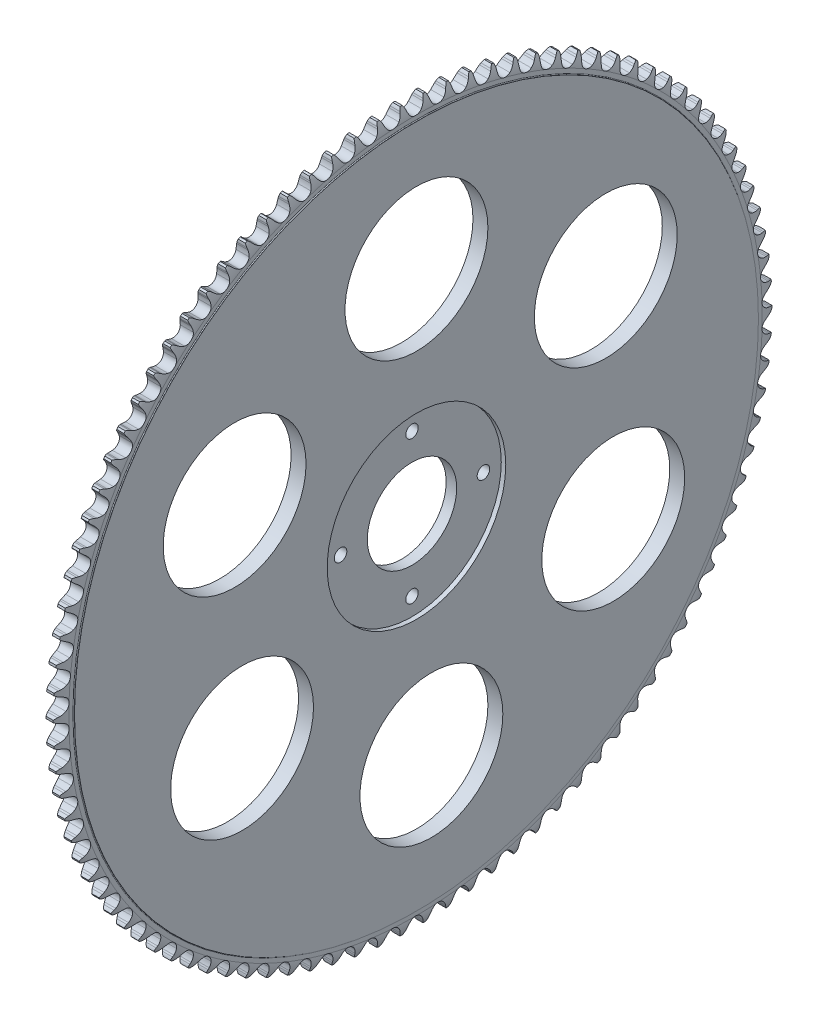
SolidWorks part; units mm, degrees
material "45"
ref_plane "前视基准面" through (0, 0, 0) normal (0, 0, 1) x (1, 0, 0)
ref_plane "上视基准面" through (0, 0, 0) normal (0, 1, 0) x (1, 0, 0)
ref_plane "右视基准面" through (0, 0, 0) normal (1, 0, 0) x (0, 0, -1)
sketch "草图1" plane through (0, 0, 0) normal (0, 0, 1) x (1, 0, 0)
  line L0 (-12.7, 0) -> (12.7, 0) construction
  line L1 (-8.3587, 50) -> (-8.3587, 383)
  line L2 (-8.3587, 383) -> (-8.1517, 383)
  line L3 (-7.3237, 383.8279) -> (-7.3237, 388.2963)
  line L4 (-4.0217, 402.5) -> (4.0217, 402.5)
  line L5 (7.3237, 388.2963) -> (7.3237, 383.8279)
  line L6 (8.1517, 383) -> (8.3587, 383)
  line L7 (8.3587, 383) -> (8.3587, 50)
  line L8 (8.3587, 50) -> (-8.3587, 50)
  line L9 (0, 0) -> (0, 402.5) construction
  line L10 (-6.5678, 396.2363) -> (6.5678, 396.2363) construction
  line L11 (-6.5678, -396.2363) -> (6.5678, -396.2363) construction
  line L12 (12.7, 0) -> (110.7, 0) construction
  line L13 (-7.3237, 388.2963) -> (3.7984, 388.2963) construction
  line L14 (-7.3237, -388.2963) -> (3.7984, -388.2963) construction
  line L15 (110.7, 0) -> (126.58, 0) construction
  line L16 (126.58, 0) -> (150.71, 0) construction
  line L17 (150.71, 0) -> (166.46, 0) construction
  line L18 (166.46, 0) -> (195.75, 0) construction
  arc A0 (-4.0217, 402.5) -> (-7.3237, 388.2963) centre (18.0263, 389.8887) ccw
  arc A1 (4.0217, 402.5) -> (7.3237, 388.2963) centre (-18.0263, 389.8887) cw
  arc A2 (7.3237, 383.8279) -> (8.1517, 383) centre (8.1517, 383.8279) ccw
  arc A3 (-8.1517, 383) -> (-7.3237, 383.8279) centre (-8.1517, 383.8279) ccw
  point P30 (7.3237, 383)
  point P33 (-7.3237, 383)
  dimension "D1" = 5.2963
  dimension "rx" = 25.4
  dimension "D3" = 0.8279
  dimension "d" = 792.4727
  dimension "p" = 25.4
  dimension "z" = 98
  dimension "da" = 805
  dimension "df" = 776.5927
  dimension "dr" = 15.88
  dimension "dk" = 100
  dimension "dg" = 766
  dimension "h" = 24.13
  dimension "bf1" = 14.6475
  dimension "b1" = 15.75
  dimension "ba" = 3.302
  dimension "D2" = 1.0349
  dimension "pt" = 29.29
revolve "旋转1" add sketch "草图1" angle 360 about L0
sketch "草图2" plane through (0, 0, 0) normal (1, 0, 0) x (0, 0, -1)
  line L0 (0, 0) -> (0, 402.5) construction
  line L1 (0, 0) -> (-12.9008, 402.2932) construction
  line L2 (0, 0) -> (-25.7883, 401.673) construction
  line L3 (6.528, 391.5607) -> (172.2353, 272.8723) construction
  line L4 (9.3702, 397.1636) -> (-10.3281, 403.6338) construction
  line L5 (0, 0) -> (12.9008, 402.2932) construction
  line L6 (9.3702, 397.1636) -> (9.996, 399.0687)
  line L7 (-9.3702, 397.1636) -> (-9.996, 399.0687)
  circle A0 centre (0, 0) radius 402.5 construction
  arc A1 (6.528, 391.5607) -> (-6.528, 391.5607) centre (0, 396.2363) cw
  arc A2 (6.528, 391.5607) -> (9.3702, 397.1636) centre (-10.3281, 403.6338) ccw
  arc A3 (11.7042, 402.3298) -> (9.996, 399.0687) centre (20.6334, 395.5747) ccw
  arc A4 (-6.528, 391.5607) -> (-9.3702, 397.1636) centre (10.3281, 403.6338) cw
  arc A5 (-11.7042, 402.3298) -> (-9.996, 399.0687) centre (-20.6334, 395.5747) cw
  arc A7 (11.7042, 402.3298) -> (-11.7042, 402.3298) centre (0, 0) ccw
  dimension "r1" = 8.0297
  dimension "r3" = 11.1965
  dimension "D1" = 3.673
  dimension "D2" = 1.837
  dimension "α/2" = 54.388
  dimension "M" = 10.3281
  dimension "T" = 7.3975
  dimension "β" = 17.429
  dimension "γ/2" = 16.347
  dimension "bc" = 2.0053
extrude "切除-拉伸1" cut sketch "草图2" against normal mid plane 16.7173
pattern_circular "阵列(圆周)1" count 98 over 360 about axis through (0, 0, 0) along (1, 0, 0) of "切除-拉伸1"
sketch "草图3" plane through (0, 0, 0) normal (0, 0, 1) x (1, 0, 0)
  line L0 (8.3587, 50) -> (6.6413, 50)
  line L3 (6.6413, 50) -> (6.6413, 80.7581)
  line L4 (6.6413, 80.7581) -> (8.3587, 80.7581)
  line L5 (8.3587, 80.7581) -> (8.3587, 50)
  line L6 (0, 0) -> (9.5, 0) construction
  line L8 (-8.3587, 383) -> (-8.3587, -383) construction
  dimension "h" = 30.7581
  dimension "K" = 9.5
  dimension "L" = 15
revolve "旋转2" [suppressed] add sketch "草图3" angle 360 about L6
chamfer "倒角3" [suppressed] distance 1 angle 45
sketch "草图5" plane through (8.3587, 0, 0) normal (1, 0, 0) x (0, 0, -1)
  line L0 (0, 0) -> (0, 331.803) construction
  circle A0 centre (0, 240) radius 80
  circle A1 centre (212.0254, 127.2388) radius 80
  circle A2 centre (220.3841, -112.7612) radius 80
  circle A3 centre (16.7173, -240) radius 80
  circle A4 centre (-195.3081, -127.2388) radius 80
  circle A5 centre (-203.6668, 112.7612) radius 80
  point P16 (8.3587, 0)
  dimension "D1" = 240
  dimension "D2" = 160
  dimension "D3" = 6
extrude "切除-拉伸3" cut sketch "草图5" against normal through all
sketch "草图6" plane through (8.3587, 0, 0) normal (1, 0, 0) x (0, 0, -1)
  circle A0 centre (0, 0) radius 100
  dimension "D1" = 200
extrude "切除-拉伸4" cut sketch "草图6" against normal blind 5
hole_wizard "M16 螺纹孔1" positions "草图7" profile "草图8" tap size "M16" standard "GB" end condition through all
sketch "草图7" plane through (3.3587, 0, 0) normal (1, 0, 0) x (0, 0, -1)
  line L0 (-108.2542, 0) -> (118.9214, 0) construction
  line L2 (0, -106.4265) -> (0, 120.2108) construction
  circle A0 centre (0, 0) radius 80
  point P0 (0, 80)
  point P2 (-80, 0)
  point P4 (0, -80)
  point P6 (80, 0)
  dimension "D1" = 160
sketch "草图8" plane through (3.3587, 80, 0) normal (0, 1, 0) x (0, 0, -1)
  line L0 (0, 0) -> (0, 11.7173)
  line L1 (0, 11.7173) -> (7, 11.7173)
  line L2 (7, 11.7173) -> (7, 0)
  line L5 (7, 0) -> (0, 0)
  line L11 (0, -6.35) -> (0, 107.95) construction
  dimension "通孔螺纹孔钻头直径" = 14
  dimension "通孔螺纹孔钻头深度" = 11.7173
cosmetic thread "孔螺蚊线1" parameters "D2"=16
cosmetic thread "孔螺蚊线2" parameters "D2"=16
cosmetic thread "孔螺蚊线3" parameters "D2"=16
cosmetic thread "孔螺蚊线4" parameters "D2"=16
